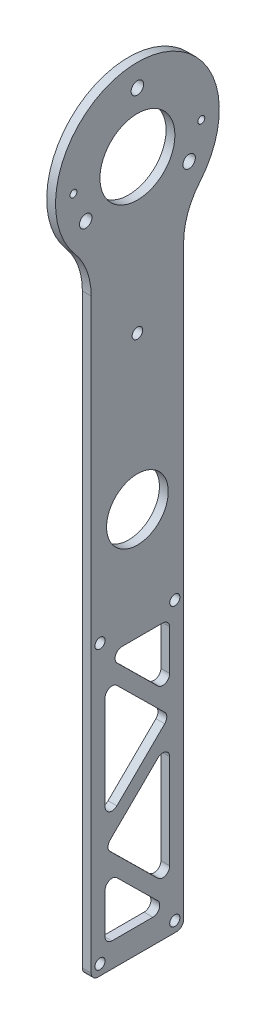
SolidWorks part; units mm, degrees
material "6061 Alloy"
ref_plane "Front Plane" through (0, 0, 0) normal (0, 0, 1) x (1, 0, 0)
ref_plane "Top Plane" through (0, 0, 0) normal (0, 1, 0) x (1, 0, 0)
ref_plane "Right Plane" through (0, 0, 0) normal (1, 0, 0) x (0, 0, -1)
sketch "Sketch1" plane through (0, 0, 0) normal (1, 0, 0) x (0, 0, -1)
  line L0 (-13.4747, 0) -> (13.4747, 0) construction
  line L1 (0, 0) -> (0, 23.8875) construction
  line L2 (-13.4747, 0) -> (-3.9926, 24.6295) construction
  line L3 (0, 35) -> (5.9803, 19.4664) construction
  line L4 (13.4747, 0) -> (-13.4747, 0) construction
  line L5 (16.645, -5) -> (-16.645, -5) construction
  line L6 (-16.645, 5.6818) -> (-10.1693, 22.5021) construction
  line L7 (1.1006, 46.0579) -> (10.3702, 21.9802) construction
  line L8 (0, 35) -> (0, 46.1125) construction
  line L9 (0, 35) -> (0, 46.1125) construction
  line L12 (-7.5, 20.1405) -> (-7.5, 43.1999) construction
  line L13 (7.5, 49.8595) -> (7.5, 43.1999) construction
  line L14 (-16.645, 35) -> (-16.645, 5.6818) construction
  line L15 (16.645, 35) -> (16.645, 5.6818) construction
  line L16 (-13.4747, 0) -> (13.4747, 0) construction
  line L17 (-13.4747, 0) -> (-13.4747, -100) construction
  line L18 (13.4747, 0) -> (13.4747, -100) construction
  line L19 (-13.4747, -100) -> (13.4747, -100) construction
  line L20 (-16.645, -5) -> (16.645, -5) construction
  line L21 (-20.7574, -5) -> (-20.7574, -103.81) construction
  line L22 (20.7574, -5) -> (20.7574, -103.81) construction
  line L23 (-16.645, -103.81) -> (16.645, -103.81)
  line L24 (-10.1693, 22.5021) -> (-8.2317, 27.535) construction
  line L25 (-16.645, 5.6818) -> (-10.3702, 21.9802) construction
  line L26 (-20.7574, -5) -> (0, 48.9165) construction
  line L27 (8.2317, 27.535) -> (10.1693, 22.5021) construction
  line L28 (10.1693, 22.5021) -> (16.645, 5.6818) construction
  line L29 (0, 48.9165) -> (20.7574, -5) construction
  line L30 (-7.5, 43.1999) -> (-7.5, 49.2605) construction
  line L31 (-7.5, 49.2605) -> (-7.5, 144.656) construction
  line L32 (7.5, 43.1999) -> (7.5, 49.2605) construction
  line L33 (7.5, 49.2605) -> (7.5, 145.344) construction
  line L34 (-1.1006, 46.0579) -> (0, 48.9165) construction
  line L35 (0, 46.1125) -> (0, 48.9165) construction
  line L36 (0, 48.9165) -> (0, 145) construction
  line L37 (0, 46.1125) -> (0, 48.9165) construction
  line L38 (0, 48.9165) -> (0, 145) construction
  line L39 (0, 48.9165) -> (1.1006, 46.0579) construction
  line L40 (-8.2317, 27.535) -> (-16.645, 5.6818) construction
  line L41 (-3.9926, 24.6295) -> (-5.9803, 19.4664) construction
  line L42 (-5.9803, 19.4664) -> (0, 35) construction
  line L43 (-13.4747, 0) -> (0, 35) construction
  line L44 (0, 23.8875) -> (0, 18.355) construction
  line L45 (0, 18.355) -> (0, 35) construction
  line L46 (5.9803, 19.4664) -> (3.9926, 24.6295) construction
  line L47 (3.9926, 24.6295) -> (13.4747, 0) construction
  line L48 (0, 35) -> (13.4747, 0) construction
  line L49 (16.645, 5.6818) -> (8.2317, 27.535) construction
  line L50 (10.3702, 21.9802) -> (16.645, 5.6818) construction
  line L51 (-10.3702, 21.9802) -> (-1.1006, 46.0579) construction
  line L52 (-7.5, 96.9583) -> (7.5, 96.9583) construction
  line L53 (-16.645, -103.81) -> (-16.645, 120.6444)
  line L54 (16.645, -103.81) -> (16.645, 120.6444)
  line L55 (-20.7574, -103.81) -> (-16.645, -103.81) construction
  line L56 (16.645, -103.81) -> (20.7574, -103.81) construction
  line L57 (16.645, 5.6818) -> (20.7574, -5) construction
  line L58 (20.7574, -5) -> (16.645, -5) construction
  line L59 (20.7574, -5) -> (-20.7574, -5) construction
  line L60 (16.645, -5) -> (20.7574, -5) construction
  line L61 (-20.7574, -5) -> (-16.645, 5.6818) construction
  line L62 (-16.645, -5) -> (-20.7574, -5) construction
  line L63 (-20.7574, -5) -> (-16.645, -5) construction
  line L64 (0, 145) -> (0, 166.5) construction
  circle A0 centre (-13.4747, 0) radius 1.8288
  circle A1 centre (0, 35) radius 11.1125
  circle A2 centre (13.4747, 0) radius 1.8288
  circle A3 centre (0, 145) radius 3 construction
  arc A6 (-7.5, 20.1405) -> (-10.3702, 21.9802) centre (0, 35) ccw construction
  arc A7 (7.5, 145.344) -> (-7.5, 144.656) centre (0, 145) ccw construction
  circle A8 centre (-13.4747, -100) radius 1.8288
  circle A9 centre (13.4747, -100) radius 1.8288
  circle A10 centre (0, 145) radius 21.5 construction
  circle A11 centre (0, 166.5) radius 2.65 construction
  circle A12 centre (-18.6195, 134.25) radius 2.65 construction
  circle A13 centre (18.6195, 134.25) radius 2.65 construction
  arc A14 (0, 166.5) -> (-18.6195, 134.25) centre (0, 145) ccw construction
  arc A15 (0, 166.5) -> (18.6195, 134.25) centre (0, 145) cw construction
  arc A16 (-18.6195, 134.25) -> (18.6195, 134.25) centre (0, 145) ccw construction
  circle A17 centre (0, 145) radius 13.5
  arc A18 (16.645, 120.6444) -> (-16.645, 120.6444) centre (0, 145) ccw
  arc A19 (10.1693, 22.5021) -> (7.5, 49.2605) centre (0, 35) ccw construction
  arc A20 (-10.1693, 22.5021) -> (-5.789, 19.9634) centre (0, 35) ccw construction
  circle A21 centre (0, 35) radius 16.1125 construction
  arc A22 (-5.789, 19.9634) -> (0, 18.8875) centre (0, 35) ccw construction
  arc A23 (0, 18.8875) -> (5.789, 19.9634) centre (0, 35) ccw construction
  arc A24 (5.789, 19.9634) -> (10.1693, 22.5021) centre (0, 35) ccw construction
  arc A25 (0, 51.1125) -> (-7.5, 49.2605) centre (0, 35) ccw construction
  arc A26 (-7.5, 49.2605) -> (-10.1693, 22.5021) centre (0, 35) ccw construction
  arc A27 (7.5, 49.2605) -> (0, 51.1125) centre (0, 35) ccw construction
  arc A28 (5.9803, 19.4664) -> (10.3702, 21.9802) centre (0, 35) ccw construction
  arc A29 (10.3702, 21.9802) -> (7.5, 49.8595) centre (0, 35) ccw construction
  arc A30 (-5.9803, 19.4664) -> (0, 18.355) centre (0, 35) ccw construction
  arc A31 (0, 18.355) -> (5.9803, 19.4664) centre (0, 35) ccw construction
  arc A32 (-10.3702, 21.9802) -> (-5.9803, 19.4664) centre (0, 35) ccw construction
  arc A33 (-16.645, 120.6444) -> (-7.5, 116.4693) centre (0, 145) ccw construction
  arc A34 (-7.5, 116.4693) -> (0, 115.5) centre (0, 145) ccw construction
  arc A35 (0, 115.5) -> (7.5, 116.4693) centre (0, 145) ccw construction
  arc A36 (7.5, 116.4693) -> (16.645, 120.6444) centre (0, 145) ccw construction
  point P4 (0, 0)
  point P34 (0, 145)
  point P67 (0, 96.9583)
  point P76 (0, 0)
  point P77 (0, 0)
  dimension "D3" = 3.6576
  dimension "D4" = 22.225
  dimension "D7" = 6
  dimension "D11" = 43
  dimension "D12" = 5.3
  dimension "D13" = 27
  dimension "D14" = 59
  dimension "D16" = 16.645
  dimension "D1" = 26.9494
  dimension "D5" = 110
  dimension "D6" = 15
  dimension "D8" = 100
  dimension "D9" = 3.81
  dimension "D10" = 35
  dimension "D15" = 5
  dimension "D2" = 5
extrude "Boss-Extrude1" add sketch "Sketch1" along normal blind 3.175 contours A6 L14 L6 | A6 L28 L15 | A26 L31 A6 L6 | A19 L28 A6 L33 | A18 L31 A6 L33 | L54 A18 L53 L23 A0 A1 A2 A8 A9 A11 A12 A13 A17 region at (0, 8.4172, 13.8)
sketch "Sketch2" plane through (3.175, 0, 0) normal (1, 0, 0) x (0, 0, -1)
  line L0 (-11.645, -5) -> (11.645, -5) construction
  line L1 (-11.645, -95) -> (11.645, -95) construction
  line L2 (11.645, -95) -> (11.645, -5) construction
  line L3 (-11.645, -95) -> (-11.645, -5) construction
  line L6 (11.645, -38.5118) -> (-11.645, -61.4882) construction
  line L7 (11.645, -5) -> (-11.645, -5)
  line L8 (-11.645, -5) -> (11.645, -27.9764)
  line L9 (11.645, -27.9764) -> (11.645, -5)
  line L10 (-11.645, -12.0236) -> (11.645, -35)
  line L11 (11.645, -35) -> (-11.645, -57.9764)
  line L12 (-11.645, -57.9764) -> (-11.645, -35)
  line L13 (-11.645, -35) -> (-11.645, -12.0236)
  line L14 (-11.645, -72.0236) -> (-11.645, -95)
  line L15 (-11.645, -95) -> (11.645, -95)
  line L16 (11.645, -95) -> (-11.645, -72.0236)
  line L17 (11.645, -42.0236) -> (11.645, -65)
  line L18 (11.645, -65) -> (11.645, -87.9764)
  line L19 (11.645, -87.9764) -> (-11.645, -65)
  line L20 (-11.645, -65) -> (11.645, -42.0236)
  line L21 (16.645, -1056.0877) -> (16.645, 48943.9123) construction
  line L22 (-16.645, -1060.2922) -> (-16.645, 48939.7078) construction
  line L23 (16.645, 23.8875) -> (-16.645, 23.8875) construction
  line L24 (-20.7574, -103.81) -> (-16.645, -103.81)
  line L25 (-20.7574, -103.81) -> (-20.7574, 23.8875)
  line L26 (-16.645, -103.81) -> (-16.645, 23.8875)
  line L27 (-20.7574, 23.8875) -> (-16.645, 23.8875)
  line L28 (-16.645, -103.81) -> (16.645, -103.81) construction
  line L29 (20.7574, -103.81) -> (16.645, -103.81)
  line L30 (20.7574, -103.81) -> (20.7574, 23.8875)
  line L31 (16.645, -103.81) -> (16.645, 23.8875)
  line L32 (20.7574, 23.8875) -> (16.645, 23.8875)
  circle A0 centre (13.4747, 0) radius 1.8288 construction
  circle A1 centre (13.4747, -100) radius 1.8288 construction
  circle A2 centre (0, 35) radius 11.1125 construction
  point P6 (11.645, -50)
  point P10 (0, 23.8875)
  point P21 (0, -50)
  point P41 (0, 0)
  point P43 (0, 0)
  dimension "D1" = 33.29
  dimension "D2" = 5
  dimension "D3" = 5
  dimension "D4" = 5
  dimension "D5" = 5
  dimension "D6" = 2.5
  dimension "D8" = 5
  dimension "D7" = 2
extrude "Cut-Extrude1" cut sketch "Sketch2" against normal up to next contours L15 L16 L14 | L20 L19 L18 L17 | L13 L12 L11 L10 | L8 L9 L7 region at (3.175, -12.6588, -3.8817) region at (3.175, -35, 3.8817) region at (3.175, -87.3412, 3.8817) region at (3.175, -65, -3.8817)
fillet "Fillet3" radius 2.5 14 edges at (1.5875, -57.9764, 11.645) (1.5875, -35, -11.645) (1.5875, -95, -11.645) (1.5875, -72.0236, 11.645) (1.5875, -95, 11.645) (1.5875, -27.9764, -11.645) (1.5875, -5, -11.645) (1.5875, -12.0236, 11.645) (1.5875, -5, 11.645) (1.5875, -87.9764, -11.645) (1.5875, -42.0236, -11.645) (1.5875, -65, 11.645) (1.5875, -103.81, -16.645) (1.5875, -103.81, 16.645)
fillet "Fillet4" radius 25 2 edges at (1.5875, 120.6444, 16.645) (1.5875, 120.6444, -16.645)
hole_wizard "M3x0.5 Tapped Hole1" positions "Sketch3" profile "Sketch4" tap size "M3x0.5" standard "ANSI Metric" end condition up to next
sketch "Sketch3" plane through (3.175, 0, 0) normal (1, 0, 0) x (0, 0, -1)
  line L2 (0, 145) -> (50000, 145) construction
  circle A0 centre (0, 145) radius 23.015 construction
  point P15 (-23.015, 145)
  point P17 (23.015, 145)
  point P18 (0, 0)
  point P19 (0, 0)
  point P20 (0, 0)
  dimension "D1" = 46.03
sketch "Sketch4" plane through (3.175, 145, -23.015) normal (0, 1, 0) x (0, 0, -1)
  line L0 (0, 0) -> (0, 3.175)
  line L1 (0, 3.175) -> (1.25, 3.175)
  line L2 (1.25, 3.175) -> (1.25, 0)
  line L5 (1.25, 0) -> (0, 0)
  line L11 (0, -6.35) -> (0, 107.95) construction
  dimension "Thru Tap Drill Dia." = 2.5
  dimension "Thru Tap Drill Depth" = 3.175
cosmetic thread "Hole Thread1" parameters "D2"=3
cosmetic thread "Hole Thread2" parameters "D2"=3
hole_wizard "M4 Clearance Hole2" positions "Sketch7" profile "Sketch8" hole size "M4" standard "ANSI Metric" end condition up to next
sketch "Sketch7" plane through (3.175, 0, 0) normal (1, 0, 0) x (0, 0, -1)
  point P0 (0, 166.5)
  point P3 (18.6195, 134.25)
  point P6 (-18.6195, 134.25)
sketch "Sketch8" plane through (3.175, 166.5, 0) normal (0, 1, 0) x (0, 0, -1)
  line L0 (0, 0) -> (0, 3.175)
  line L1 (0, 3.175) -> (2.25, 3.175)
  line L2 (2.25, 3.175) -> (2.25, 0)
  line L5 (2.25, 0) -> (0, 0)
  line L11 (0, -6.35) -> (0, 107.95) construction
  dimension "Thru Hole Dia." = 4.5
  dimension "Thru Hole Depth" = 3.175
hole_wizard "#6 Clearance Hole1" positions "Sketch5" profile "Sketch6" hole size "#6" standard "ANSI Inch" end condition through all
sketch "Sketch5" plane through (3.175, 0, 0) normal (1, 0, 0) x (0, 0, -1)
  circle A0 centre (0, 35) radius 11.1125 construction
  point P0 (0, 90)
  dimension "D1" = 55
sketch "Sketch6" plane through (3.175, 90, 0) normal (0, 1, 0) x (0, 0, -1)
  line L0 (0, 0) -> (0, 3.175)
  line L1 (0, 3.175) -> (1.8986, 3.175)
  line L2 (1.8986, 3.175) -> (1.8986, 0)
  line L5 (1.8986, 0) -> (0, 0)
  line L11 (0, -6.35) -> (0, 107.95) construction
  dimension "Thru Hole Dia." = 3.7973
  dimension "Thru Hole Depth" = 3.175
